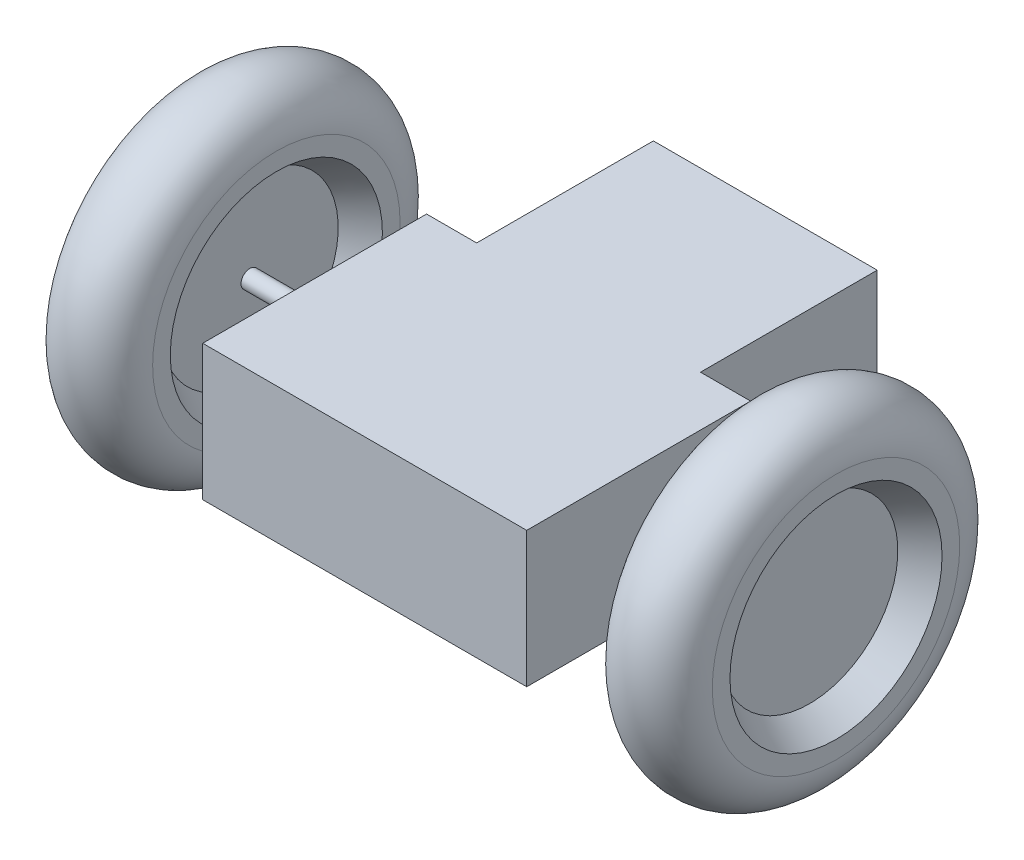
SolidWorks part; units mm, degrees
ref_plane "Front Plane" through (0, 0, 0) normal (0, 0, 1) x (1, 0, 0)
ref_plane "Top Plane" through (0, 0, 0) normal (0, 1, 0) x (1, 0, 0)
ref_plane "Right Plane" through (0, 0, 0) normal (1, 0, 0) x (0, 0, -1)
sketch "Sketch1" plane through (0, 0, 0) normal (0, 1, 0) x (1, 0, 0)
  line L1 (27.5, 34) -> (-27.5, 34)
  line L2 (27.5, 34) -> (27.5, -34)
  line L3 (27.5, -34) -> (-27.5, -34)
  line L4 (-27.5, 34) -> (-27.5, -34)
  line L5 (27.5, 34) -> (-27.5, -34) construction
  line L6 (27.5, -34) -> (-27.5, 34) construction
  point P0 (0, 0)
  dimension "D1" = 55
  dimension "D2" = 68
extrude "Boss-Extrude1" add sketch "Sketch1" along normal blind 11.5 and the other way blind 11.5
sketch "Sketch2" plane through (27.5, 0, 0) normal (1, 0, 0) x (0, 0, -1)
  line L0 (-40, 0) -> (49960, 0) construction
  line L1 (-34, 11.5) -> (-34, -11.5) construction
  circle A0 centre (-9, 0) radius 1.5
  point P4 (-34, 0)
  dimension "D2" = 3
  dimension "D1" = 25
extrude "Boss-Extrude2" add sketch "Sketch2" along normal blind 12.5
sketch "Sketch6" plane through (0, 0, 0) normal (0, 1, 0) x (1, 0, 0)
  line L0 (40, -7.5) -> (44.5, -7.5)
  line L1 (44.5, -7.5) -> (44.5, 6)
  line L2 (44.5, 6) -> (40, 9)
  line L3 (40, 9) -> (40, 12)
  line L4 (55, 12) -> (55, 9)
  line L5 (55, 9) -> (50.5, 6)
  line L6 (50.5, 6) -> (50.5, -9)
  line L7 (50.5, -9) -> (40, -9)
  line L8 (40, -9) -> (40, -7.5)
  line L9 (47.5, 0.5303) -> (47.5, -49999.4697) construction
  line L10 (42.5, 9) -> (50042.5, 9) construction
  line L11 (45, 6) -> (50045, 6) construction
  line L12 (40, -10.5) -> (40, -7.5) construction
  line L13 (42.5, -9) -> (50042.5, -9) construction
  arc A0 (40, 12) -> (55, 12) centre (47.5, 12) cw
  point P23 (40, -9)
  dimension "D1" = 21
  dimension "D2" = 7.5
  dimension "D3" = 6
  dimension "D4" = 3
  dimension "D5" = 3
revolve "Revolve1" add sketch "Sketch6" angle 360 about L13
mirror "Mirror1" about plane through (0, 0, 0) normal (1, 0, 0) of "Revolve1", "Boss-Extrude2"
sketch "Sketch7" plane through (0, 11.5, 0) normal (0, 1, 0) x (1, 0, 0)
  line L0 (0, 0) -> (0, 50000) construction
  line L1 (-27.5, 34) -> (-19, 34)
  line L2 (-27.5, 34) -> (-27.5, 4)
  line L3 (-27.5, 4) -> (-19, 4)
  line L4 (-19, 34) -> (-19, 4)
  line L5 (27.5, 34) -> (19, 34)
  line L6 (27.5, 34) -> (27.5, 4)
  line L7 (27.5, 4) -> (19, 4)
  line L8 (19, 34) -> (19, 4)
  dimension "D1" = 38
  dimension "D2" = 30
extrude "Cut-Extrude1" cut sketch "Sketch7" against normal through all
sketch "Sketch8" plane through (0, -11.5, 0) normal (0, -1, 0) x (1, 0, 0)
  line L0 (-27.5, -4) -> (-27.5, 34) construction
  line L1 (-27.5, 19) -> (-32.5, 19)
  line L2 (-27.5, 19) -> (-27.5, 11)
  line L3 (-27.5, 11) -> (-32.5, 11)
  line L4 (-32.5, 19) -> (-32.5, 11)
  line L5 (27.5, 34) -> (27.5, -4) construction
  line L6 (27.5, 19) -> (32.5, 19)
  line L7 (27.5, 19) -> (27.5, 11)
  line L8 (27.5, 11) -> (32.5, 11)
  line L9 (32.5, 19) -> (32.5, 11)
  line L10 (0, 0) -> (0, -50000) construction
  line L12 (27.5, 15) -> (-49972.5, 15) construction
  line L13 (-27.5, 34) -> (27.5, 34) construction
  circle A0 centre (30, 15) radius 1.5
  circle A1 centre (-30, 15) radius 1.5
  point P17 (27.5, 15)
  dimension "D5" = 3
  dimension "D1" = 5
  dimension "D2" = 8
  dimension "D3" = 19
  dimension "D4" = 60
extrude "Boss-Extrude3" add sketch "Sketch8" against normal blind 2
